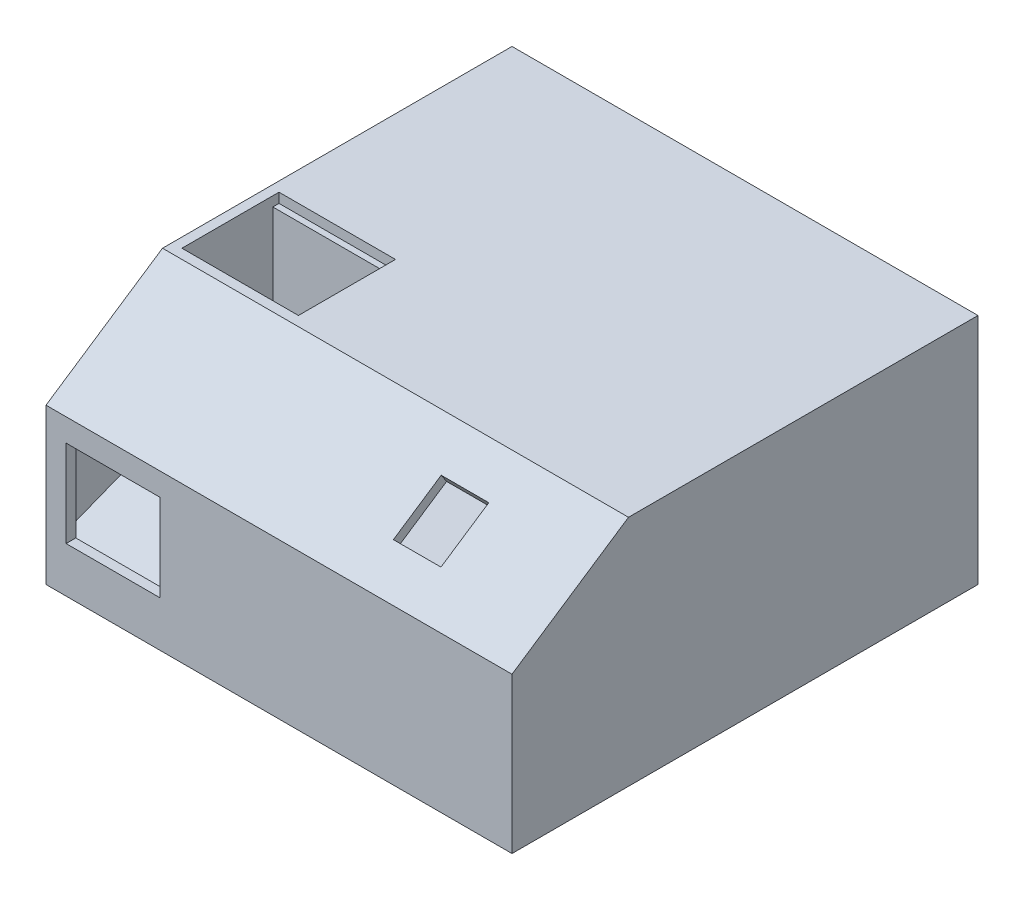
SolidWorks part; units mm, degrees
ref_plane "Front Plane" through (0, 0, 0) normal (0, 0, 1) x (1, 0, 0)
ref_plane "Top Plane" through (0, 0, 0) normal (0, 1, 0) x (1, 0, 0)
ref_plane "Right Plane" through (0, 0, 0) normal (1, 0, 0) x (0, 0, -1)
sketch "Sketch1" plane through (0, 0, 0) normal (0, 1, 0) x (1, 0, 0)
  line L0 (-304.8, 0) -> (304.8, 0) construction
  line L1 (-304.8, 304.8) -> (304.8, 304.8)
  line L2 (-304.8, 304.8) -> (-304.8, -304.8)
  line L3 (-304.8, -304.8) -> (304.8, -304.8)
  line L4 (304.8, 304.8) -> (304.8, -304.8)
  line L5 (-304.8, -304.8) -> (304.8, -304.8) construction
  point P6 (0, 0)
  point P7 (-260.9278, -304.8)
  dimension "D1" = 609.6
  dimension "D2" = 609.6
extrude "Boss-Extrude1" add sketch "Sketch1" along normal blind 304.8 contours L2 L1 L4 L3
sketch "Sketch9" plane through (0, 304.8, 0) normal (0, 1, 0) x (1, 0, 0)
  line L0 (-304.8, -152.4) -> (304.8, -152.4) construction
  line L1 (-304.8, 304.8) -> (-304.8, -304.8) construction
  line L2 (304.8, 304.8) -> (304.8, -304.8) construction
  line L3 (-304.8, -304.8) -> (304.8, -304.8) construction
  dimension "D1" = 152.4
sketch "Sketch10" plane through (0, 0, 304.8) normal (0, 0, 1) x (1, 0, 0)
  line L0 (-304.8, 203.2) -> (304.8, 203.2) construction
  line L1 (-304.8, 304.8) -> (-304.8, 0) construction
  line L2 (304.8, 304.8) -> (304.8, 0) construction
  line L3 (-304.8, 0) -> (304.8, 0) construction
  dimension "D1" = 203.2
sketch "Sketch11" plane through (304.8, 0, 0) normal (1, 0, 0) x (0, 0, -1)
  line L0 (-304.8, 203.2) -> (-152.4, 304.8)
extrude "Cut-Extrude2" cut sketch "Sketch11" against normal blind 609.6 and the other way through all contours L0
shell "Shell11" thickness 12.7 removed face at (0, 152.4, -304.8)
sketch "Sketch12" plane through (0, 281.3538, 187.5692) normal (0, 0.8321, 0.5547) x (1, 0, 0)
  line L0 (304.8, 42.2682) -> (304.8, -140.8938) construction
  line L1 (304.8, -49.3128) -> (93.8907, -49.3128) construction
  line L3 (104.7321, -11.7208) -> (166.9621, -11.7208)
  line L4 (104.7321, -11.7208) -> (104.7321, -86.9048)
  line L5 (104.7321, -86.9048) -> (166.9621, -86.9048)
  line L6 (166.9621, -11.7208) -> (166.9621, -86.9048)
  point P10 (166.9621, -49.3128)
  dimension "D1" = 62.23
  dimension "D2" = 75.184
extrude "Cut-Extrude5" cut sketch "Sketch12" against normal up to next
sketch "Sketch13" plane through (0, 304.8, 0) normal (0, 1, 0) x (1, 0, 0)
  line L0 (-292.1, -139.7) -> (-292.1, -12.7)
  line L1 (-304.8, -152.4) -> (-127, -152.4) construction
  line L2 (-304.8, -152.4) -> (-304.8, 0) construction
  line L3 (-304.8, 0) -> (-127, 0) construction
  line L4 (-127, -152.4) -> (-127, 0) construction
  line L5 (-292.1, -12.7) -> (-139.7, -12.7)
  line L6 (-139.7, -139.7) -> (-139.7, -12.7)
  line L7 (-292.1, -139.7) -> (-139.7, -139.7)
  dimension "D1" = 177.8
  dimension "D2" = 152.4
  dimension "D3" = 12.7
extrude "Cut-Extrude6" cut sketch "Sketch13" against normal up to next
sketch "Sketch14" plane through (-292.1, 0, 0) normal (1, 0, 0) x (0, 0, -1)
  line L0 (-292.1, 12.7) -> (-8.0968, 12.7)
  line L1 (-148.5547, 292.1) -> (-8.0968, 292.1)
  line L4 (-8.0968, 292.1) -> (-8.0968, 12.7)
  line L5 (304.8, 12.7) -> (-292.1, 12.7) construction
  line L6 (-148.5547, 292.1) -> (-292.1, 196.4032)
  line L7 (-292.1, 196.4032) -> (-292.1, 12.7)
  point P2 (0, 0)
  point P4 (-8.0968, 12.7)
extrude "Boss-Extrude2" add sketch "Sketch14" along normal blind 158.496 contours L4 L0 L7 L6 L1
shell "Shell13" thickness 12.7 removed face at (-215.9, 292.1, 76.2)
sketch "Sketch15" plane through (-292.1, 0, 0) normal (1, 0, 0) x (0, 0, -1)
  line L0 (-292.1, 59.5443) -> (-20.7968, 166.8823)
  line L1 (-292.1, 196.4032) -> (-292.1, 12.7) construction
  line L2 (-20.7968, 292.1) -> (-20.7968, 12.7) construction
  line L3 (-292.1, 51.4235) -> (-20.7968, 158.7615)
  line L4 (-292.1, 59.5443) -> (-292.1, 51.4235)
  line L5 (-20.7968, 166.8823) -> (-20.7968, 158.7615)
extrude "Boss-Extrude4" add sketch "Sketch15" along normal up to next
sketch "Sketch16" plane through (0, 0, 292.1) normal (0, 0, -1) x (-1, 0, 0)
  line L0 (146.304, 59.5443) -> (292.1, 59.5443) construction
  line L1 (278.5685, 59.5443) -> (155.5421, 59.5443)
  line L2 (278.5685, 59.5443) -> (278.5685, 173.3815)
  line L3 (278.5685, 173.3815) -> (155.5421, 173.3815)
  line L4 (155.5421, 59.5443) -> (155.5421, 173.3815)
extrude "Cut-Extrude7" cut sketch "Sketch16" against normal blind 158.496
